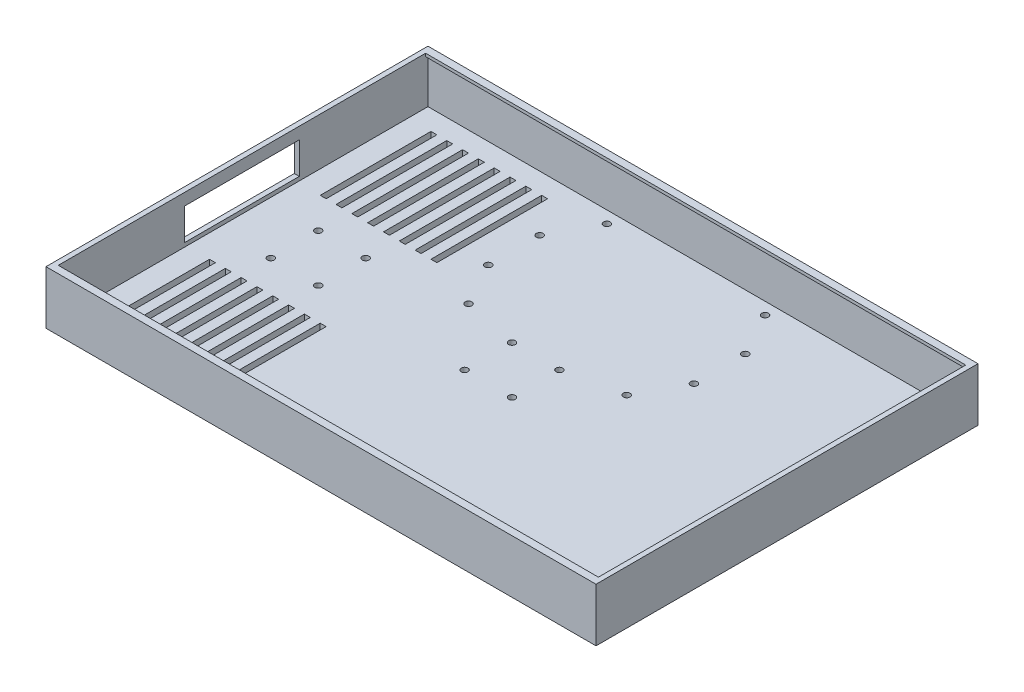
SolidWorks part; units mm, degrees
ref_plane "Front Plane" through (0, 0, 0) normal (0, 0, 1) x (1, 0, 0)
ref_plane "Top Plane" through (0, 0, 0) normal (0, 1, 0) x (1, 0, 0)
ref_plane "Right Plane" through (0, 0, 0) normal (1, 0, 0) x (0, 0, -1)
sketch "Sketch1" plane through (0, 0, 0) normal (0, 1, 0) x (1, 0, 0)
  line L1 (-139.1, -96.6) -> (139.1, -96.6)
  line L2 (-139.1, -96.6) -> (-139.1, 96.6)
  line L3 (-139.1, 96.6) -> (139.1, 96.6)
  line L4 (139.1, -96.6) -> (139.1, 96.6)
  line L5 (-139.1, -96.6) -> (139.1, 96.6) construction
  line L6 (-139.1, 96.6) -> (139.1, -96.6) construction
  point P0 (0, 0)
  dimension "D1" = 278.2
  dimension "D2" = 193.2
extrude "Shell Block" add sketch "Sketch1" along normal blind 27
ref_plane "Shell Front" through (0, 27, 0) normal (0, 1, 0) x (1, 0, 0)
sketch "Sketch2" plane through (0, 27, 0) normal (0, 1, 0) x (1, 0, 0)
  line L1 (-136.6, -92.9) -> (136.6, -92.9)
  line L2 (-136.6, -92.9) -> (-136.6, 92.9)
  line L3 (-136.6, 92.9) -> (136.6, 92.9)
  line L4 (136.6, -92.9) -> (136.6, 92.9)
  line L5 (-136.6, -92.9) -> (136.6, 92.9) construction
  line L6 (-136.6, 92.9) -> (136.6, -92.9) construction
  point P0 (0, 0)
  dimension "D1" = 273.2
  dimension "D2" = 185.8
extrude "Front Opening" cut sketch "Sketch2" against normal blind 1.5
ref_plane "Under Lip" through (0, 25.5, 0) normal (0, 1, 0) x (1, 0, 0)
sketch "Sketch3" plane through (0, 25.5, 0) normal (0, 1, 0) x (1, 0, 0)
  line L1 (-136.6, -94.1) -> (136.6, -94.1)
  line L2 (-136.6, -94.1) -> (-136.6, 94.1)
  line L3 (-136.6, 94.1) -> (136.6, 94.1)
  line L4 (136.6, -94.1) -> (136.6, 94.1)
  line L5 (-136.6, -94.1) -> (136.6, 94.1) construction
  line L6 (-136.6, 94.1) -> (136.6, -94.1) construction
  point P0 (0, 0)
  dimension "D1" = 273.2
  dimension "D2" = 188.2
extrude "Display Pocket" cut sketch "Sketch3" against normal blind 22.5
ref_plane "Back Inner" through (0, 3, 0) normal (0, 1, 0) x (1, 0, 0)
sketch "Sketch4" plane through (0, 3, 0) normal (0, 1, 0) x (1, 0, 0)
  line L1 (-69, 28) -> (-66, 28)
  line L2 (-69, 28) -> (-69, 84)
  line L3 (-69, 84) -> (-66, 84)
  line L4 (-66, 28) -> (-66, 84)
  line L6 (-69, -84) -> (-66, -84)
  line L7 (-69, -84) -> (-69, -28)
  line L8 (-69, -28) -> (-66, -28)
  line L9 (-66, -84) -> (-66, -28)
  line L11 (-77, 28) -> (-74, 28)
  line L12 (-77, 28) -> (-77, 84)
  line L13 (-77, 84) -> (-74, 84)
  line L14 (-74, 28) -> (-74, 84)
  line L16 (-77, -84) -> (-74, -84)
  line L17 (-77, -84) -> (-77, -28)
  line L18 (-77, -28) -> (-74, -28)
  line L19 (-74, -84) -> (-74, -28)
  line L21 (-85, 28) -> (-82, 28)
  line L22 (-85, 28) -> (-85, 84)
  line L23 (-85, 84) -> (-82, 84)
  line L24 (-82, 28) -> (-82, 84)
  line L26 (-85, -84) -> (-82, -84)
  line L27 (-85, -84) -> (-85, -28)
  line L28 (-85, -28) -> (-82, -28)
  line L29 (-82, -84) -> (-82, -28)
  line L31 (-93, 28) -> (-90, 28)
  line L32 (-93, 28) -> (-93, 84)
  line L33 (-93, 84) -> (-90, 84)
  line L34 (-90, 28) -> (-90, 84)
  line L36 (-93, -84) -> (-90, -84)
  line L37 (-93, -84) -> (-93, -28)
  line L38 (-93, -28) -> (-90, -28)
  line L39 (-90, -84) -> (-90, -28)
  line L41 (-101, 28) -> (-98, 28)
  line L42 (-101, 28) -> (-101, 84)
  line L43 (-101, 84) -> (-98, 84)
  line L44 (-98, 28) -> (-98, 84)
  line L46 (-101, -84) -> (-98, -84)
  line L47 (-101, -84) -> (-101, -28)
  line L48 (-101, -28) -> (-98, -28)
  line L49 (-98, -84) -> (-98, -28)
  line L51 (-109, 28) -> (-106, 28)
  line L52 (-109, 28) -> (-109, 84)
  line L53 (-109, 84) -> (-106, 84)
  line L54 (-106, 28) -> (-106, 84)
  line L56 (-109, -84) -> (-106, -84)
  line L57 (-109, -84) -> (-109, -28)
  line L58 (-109, -28) -> (-106, -28)
  line L59 (-106, -84) -> (-106, -28)
  line L61 (-117, 28) -> (-114, 28)
  line L62 (-117, 28) -> (-117, 84)
  line L63 (-117, 84) -> (-114, 84)
  line L64 (-114, 28) -> (-114, 84)
  line L66 (-117, -84) -> (-114, -84)
  line L67 (-117, -84) -> (-117, -28)
  line L68 (-117, -28) -> (-114, -28)
  line L69 (-114, -84) -> (-114, -28)
  line L71 (-125, 28) -> (-122, 28)
  line L72 (-125, 28) -> (-125, 84)
  line L73 (-125, 84) -> (-122, 84)
  line L74 (-122, 28) -> (-122, 84)
  line L76 (-125, -84) -> (-122, -84)
  line L77 (-125, -84) -> (-125, -28)
  line L78 (-125, -28) -> (-122, -28)
  line L79 (-122, -84) -> (-122, -28)
extrude "Vent Slots" cut sketch "Sketch4" against normal blind 4
sketch "Sketch5" plane through (0, 0, 0) normal (1, 0, 0) x (0, 0, -1)
  line L1 (-29, 5) -> (29, 5)
  line L2 (-29, 5) -> (-29, 21)
  line L3 (-29, 21) -> (29, 21)
  line L4 (29, 5) -> (29, 21)
extrude "Cable Exit (-X short side)" cut sketch "Sketch5" against normal blind 140.1
sketch "Sketch6" plane through (0, 3, 0) normal (0, 1, 0) x (1, 0, 0)
  circle A0 centre (-40, 18) radius 1.7
  circle A1 centre (-40, 88) radius 1.7
  circle A2 centre (40, 18) radius 1.7
  circle A3 centre (40, 88) radius 1.7
  circle A4 centre (-52, 40) radius 1.7
  circle A5 centre (-52, 66) radius 1.7
  circle A6 centre (52, 40) radius 1.7
  circle A7 centre (52, 66) radius 1.7
  circle A8 centre (-12, -82) radius 1.7
  circle A9 centre (12, -82) radius 1.7
  circle A10 centre (124, -12) radius 1.7
  circle A11 centre (124, 12) radius 1.7
  circle A12 centre (-12, -12) radius 1.7
  circle A13 centre (-12, 12) radius 1.7
  circle A14 centre (12, -12) radius 1.7
  circle A15 centre (12, 12) radius 1.7
  circle A16 centre (-110, 12) radius 1.7
  circle A17 centre (-110, -12) radius 1.7
  circle A18 centre (-86, 12) radius 1.7
  circle A19 centre (-86, -12) radius 1.7
extrude "Bolt Holes" cut sketch "Sketch6" against normal blind 4
equation "\"DispL\" = 272.0"
equation "\"DispW\" = 187.0"
equation "\"DispT\" = 20.0"
equation "\"Clr\" = 0.6"
equation "\"Wall\" = 2.5"
equation "\"BackT\" = 3.0"
equation "\"CableRoom\" = 4.0"
equation "\"LipW\" = 1.2"
equation "\"LipT\" = 1.5"
equation "\"CableW\" = 58.0"
equation "\"CableH\" = 16.0"
equation "\"BoltD\" = 3.4"
equation "\"ShellL\" = \"DispL\" + 2 * \"Clr\" + 2 * \"Wall\""
equation "\"ShellW\" = \"DispW\" + 2 * \"Clr\" + 2 * \"Wall\""
equation "\"ShellH\" = \"BackT\" + \"DispT\" + \"CableRoom\""
equation "\"D1@Sketch1\" = \"ShellL\""
equation "\"D2@Sketch1\" = \"ShellW\""
equation "\"D1@Shell Block\" = \"ShellH\""
equation "\"D1@Shell Front\" = \"ShellH\""
equation "\"D1@Sketch2\" = \"DispL\" + 2 * \"Clr\""
equation "\"D2@Sketch2\" = \"DispW\" + 2 * \"Clr\" - 2 * \"LipW\""
equation "\"D1@Front Opening\" = \"LipT\""
equation "\"D1@Under Lip\" = \"ShellH\" - \"LipT\""
equation "\"D1@Sketch3\" = \"DispL\" + 2 * \"Clr\""
equation "\"D2@Sketch3\" = \"DispW\" + 2 * \"Clr\""
equation "\"D1@Display Pocket\" = \"ShellH\" - \"LipT\" - \"BackT\""
equation "\"D1@Back Inner\" = \"BackT\""
